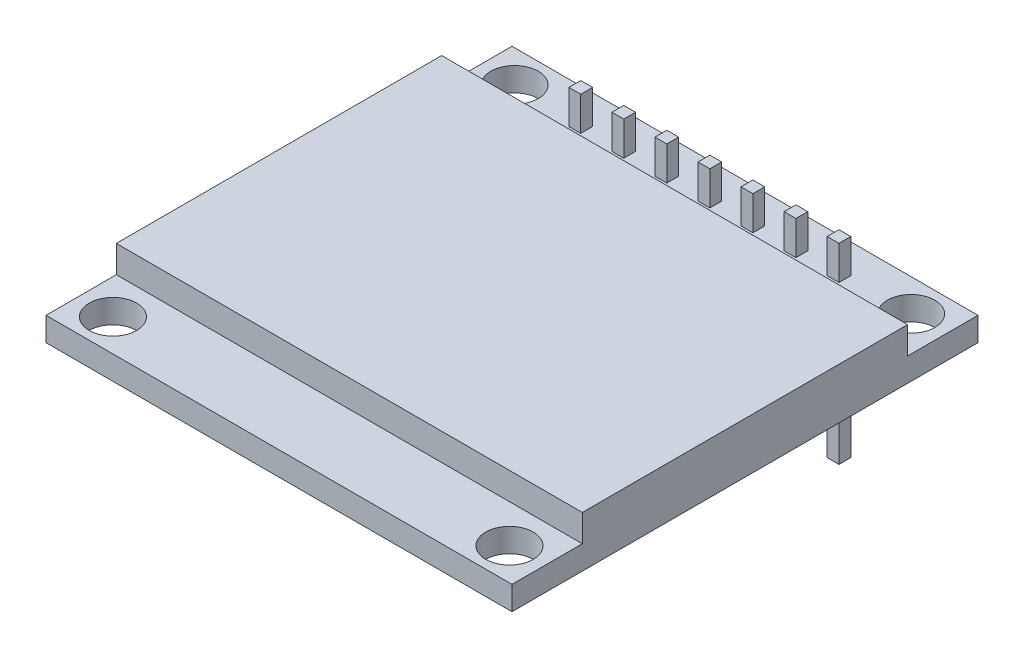
SolidWorks part; units mm, degrees
ref_plane "前视基准面" through (0, 0, 0) normal (0, 0, 1) x (1, 0, 0)
ref_plane "上视基准面" through (0, 0, 0) normal (0, 1, 0) x (1, 0, 0)
ref_plane "右视基准面" through (0, 0, 0) normal (1, 0, 0) x (0, 0, -1)
other "Configuration Table"
sketch "草图1" plane through (0, 0, 0) normal (0, 1, 0) x (1, 0, 0)
  line L1 (0, 0) -> (27.5, 0)
  line L2 (0, 0) -> (0, -27.5)
  line L3 (0, -27.5) -> (27.5, -27.5)
  line L4 (27.5, 0) -> (27.5, -27.5)
  line L9 (0, -4.15) -> (27.5, -4.15)
  line L10 (0, -4.15) -> (0, -23.35)
  line L11 (0, -23.35) -> (27.5, -23.35)
  line L12 (27.5, -4.15) -> (27.5, -23.35)
  line L13 (7.4, -0.805) -> (9.94, -0.805)
  line L18 (4.86, -0.805) -> (7.4, -0.805)
  line L19 (4.86, -0.805) -> (4.86, -3.345)
  line L20 (4.86, -3.345) -> (7.4, -3.345)
  line L21 (7.4, -0.805) -> (7.4, -3.345)
  line L22 (4.86, -0.805) -> (7.4, -3.345) construction
  line L23 (4.86, -3.345) -> (7.4, -0.805) construction
  line L24 (5.78, -2.425) -> (6.48, -2.425)
  line L25 (5.78, -2.425) -> (5.78, -1.725)
  line L26 (5.78, -1.725) -> (6.48, -1.725)
  line L27 (6.48, -2.425) -> (6.48, -1.725)
  line L28 (5.78, -2.425) -> (6.48, -1.725) construction
  line L29 (5.78, -1.725) -> (6.48, -2.425) construction
  line L30 (7.4, -0.805) -> (7.4, -3.345)
  line L31 (7.4, -3.345) -> (9.94, -3.345)
  line L32 (9.94, -0.805) -> (9.94, -3.345)
  line L33 (8.32, -2.425) -> (9.02, -2.425)
  line L34 (8.32, -2.425) -> (8.32, -1.725)
  line L35 (8.32, -1.725) -> (9.02, -1.725)
  line L36 (9.02, -2.425) -> (9.02, -1.725)
  line L37 (7.4, -0.805) -> (9.94, -3.345) construction
  line L38 (7.4, -3.345) -> (9.94, -0.805) construction
  line L39 (8.32, -2.425) -> (9.02, -1.725) construction
  line L40 (8.32, -1.725) -> (9.02, -2.425) construction
  line L41 (9.94, -0.805) -> (12.48, -0.805)
  line L42 (9.94, -0.805) -> (9.94, -3.345)
  line L43 (9.94, -3.345) -> (12.48, -3.345)
  line L44 (12.48, -0.805) -> (12.48, -3.345)
  line L45 (10.86, -2.425) -> (11.56, -2.425)
  line L46 (10.86, -2.425) -> (10.86, -1.725)
  line L47 (10.86, -1.725) -> (11.56, -1.725)
  line L48 (11.56, -2.425) -> (11.56, -1.725)
  line L49 (9.94, -0.805) -> (12.48, -3.345) construction
  line L50 (9.94, -3.345) -> (12.48, -0.805) construction
  line L51 (10.86, -2.425) -> (11.56, -1.725) construction
  line L52 (10.86, -1.725) -> (11.56, -2.425) construction
  line L53 (12.48, -0.805) -> (15.02, -0.805)
  line L54 (12.48, -0.805) -> (12.48, -3.345)
  line L55 (12.48, -3.345) -> (15.02, -3.345)
  line L56 (15.02, -0.805) -> (15.02, -3.345)
  line L57 (13.4, -2.425) -> (14.1, -2.425)
  line L58 (13.4, -2.425) -> (13.4, -1.725)
  line L59 (13.4, -1.725) -> (14.1, -1.725)
  line L60 (14.1, -2.425) -> (14.1, -1.725)
  line L61 (12.48, -0.805) -> (15.02, -3.345) construction
  line L62 (12.48, -3.345) -> (15.02, -0.805) construction
  line L63 (13.4, -2.425) -> (14.1, -1.725) construction
  line L64 (13.4, -1.725) -> (14.1, -2.425) construction
  line L65 (15.02, -0.805) -> (17.56, -0.805)
  line L66 (15.02, -0.805) -> (15.02, -3.345)
  line L67 (15.02, -3.345) -> (17.56, -3.345)
  line L68 (17.56, -0.805) -> (17.56, -3.345)
  line L69 (15.94, -2.425) -> (16.64, -2.425)
  line L70 (15.94, -2.425) -> (15.94, -1.725)
  line L71 (15.94, -1.725) -> (16.64, -1.725)
  line L72 (16.64, -2.425) -> (16.64, -1.725)
  line L73 (15.02, -0.805) -> (17.56, -3.345) construction
  line L74 (15.02, -3.345) -> (17.56, -0.805) construction
  line L75 (15.94, -2.425) -> (16.64, -1.725) construction
  line L76 (15.94, -1.725) -> (16.64, -2.425) construction
  line L77 (17.56, -0.805) -> (20.1, -0.805)
  line L78 (17.56, -0.805) -> (17.56, -3.345)
  line L79 (17.56, -3.345) -> (20.1, -3.345)
  line L80 (20.1, -0.805) -> (20.1, -3.345)
  line L81 (18.48, -2.425) -> (19.18, -2.425)
  line L82 (18.48, -2.425) -> (18.48, -1.725)
  line L83 (18.48, -1.725) -> (19.18, -1.725)
  line L84 (19.18, -2.425) -> (19.18, -1.725)
  line L85 (17.56, -0.805) -> (20.1, -3.345) construction
  line L86 (17.56, -3.345) -> (20.1, -0.805) construction
  line L87 (18.48, -2.425) -> (19.18, -1.725) construction
  line L88 (18.48, -1.725) -> (19.18, -2.425) construction
  line L89 (20.1, -0.805) -> (22.64, -0.805)
  line L90 (20.1, -0.805) -> (20.1, -3.345)
  line L91 (20.1, -3.345) -> (22.64, -3.345)
  line L92 (22.64, -0.805) -> (22.64, -3.345)
  line L93 (21.02, -2.425) -> (21.72, -2.425)
  line L94 (21.02, -2.425) -> (21.02, -1.725)
  line L95 (21.02, -1.725) -> (21.72, -1.725)
  line L96 (21.72, -2.425) -> (21.72, -1.725)
  line L97 (20.1, -0.805) -> (22.64, -3.345) construction
  line L98 (20.1, -3.345) -> (22.64, -0.805) construction
  line L99 (21.02, -2.425) -> (21.72, -1.725) construction
  line L100 (21.02, -1.725) -> (21.72, -2.425) construction
  circle A0 centre (2.05, -1.9) radius 1.4
  circle A1 centre (25.45, -1.9) radius 1.4
  circle A2 centre (2.05, -25.6) radius 1.4
  circle A3 centre (25.45, -25.6) radius 1.4
  point P9 (0, -13.75)
  point P10 (0, -13.75)
  point P19 (0, 0)
  point P20 (6.13, -2.075)
  point P25 (6.13, -2.075)
  point P27 (0, 0)
  point P28 (0, 0)
  point P33 (8.67, -2.075)
  point P38 (8.67, -2.075)
  point P43 (11.21, -2.075)
  point P48 (11.21, -2.075)
  point P53 (13.75, -2.075)
  point P58 (13.75, -2.075)
  point P63 (16.29, -2.075)
  point P68 (16.29, -2.075)
  point P73 (18.83, -2.075)
  point P78 (18.83, -2.075)
  point P83 (21.37, -2.075)
  point P88 (21.37, -2.075)
  dimension "D3" = 2.8
  dimension "D9" = 0.7
  dimension "D1" = 27.5
  dimension "D2" = 19.2
  dimension "D4" = 1.9
  dimension "D5" = 2.05
  dimension "D6" = 1.9
  dimension "D7" = 2.05
  dimension "D8" = 2.54
  dimension "D10" = 7
extrude "凸台-拉伸1" add sketch "草图1" along normal blind 1.4 contours L3 L4 L1 L2 | A0 | A1 | A2 | A3
extrude "凸台-拉伸2" add sketch "草图1<3>" along normal blind 3 contours L9 L12 L11 L10
sketch "草图1<3>" plane through (0, 0, 0) normal (0, 1, 0) x (1, 0, 0) same geometry as "草图1"
extrude "凸台-拉伸3" add sketch "草图1<4>" against normal blind 2.54 contours L89 L92 L91 L90 | L77 L80 L79 L78 | L65 L68 L67 L66 | L53 L56 L55 L54 | L41 L44 L43 L42 | L13 L32 L31 L30 | L18 L21 L20 L19
sketch "草图1<4>" plane through (0, 0, 0) normal (0, 1, 0) x (1, 0, 0) same geometry as "草图1"
extrude "凸台-拉伸4" add sketch "草图1<5>" against normal blind 11.3 from offset 3.4 contours L95 L96 L93 L94 | L83 L84 L81 L82 | L71 L72 L69 L70 | L59 L60 L57 L58 | L47 L48 L45 L46 | L35 L36 L33 L34 | L26 L27 L24 L25
sketch "草图1<5>" plane through (0, 0, 0) normal (0, 1, 0) x (1, 0, 0) same geometry as "草图1"
